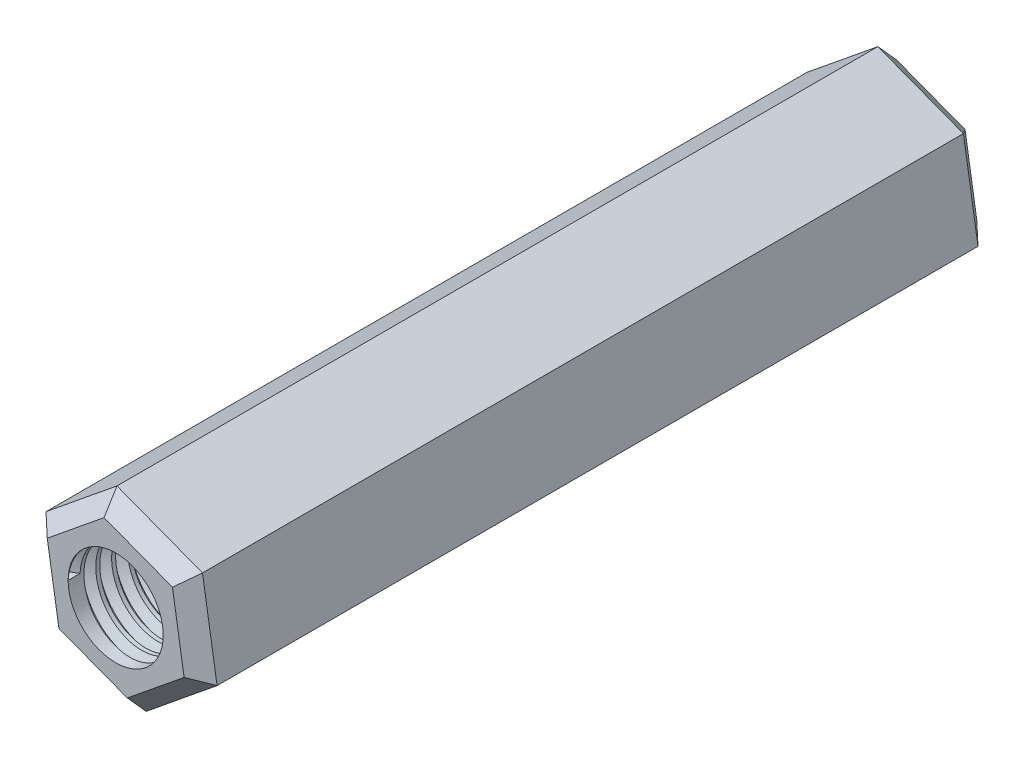
SolidWorks part; units mm, degrees
ref_plane "Plan de face" through (0, 0, 0) normal (0, 0, 1) x (1, 0, 0)
ref_plane "Plan de dessus" through (0, 0, 0) normal (0, 1, 0) x (1, 0, 0)
ref_plane "Plan de droite" through (0, 0, 0) normal (1, 0, 0) x (0, 0, -1)
sketch "Esquisse1" plane through (0, 0, 0) normal (0, 0, 1) x (1, 0, 0)
  line L1 (2.6978, -1.0272) -> (2.2385, 1.8228)
  line L2 (2.2385, 1.8228) -> (-0.4594, 2.85)
  line L3 (-0.4594, 2.85) -> (-2.6978, 1.0272)
  line L4 (-2.6978, 1.0272) -> (-2.2385, -1.8228)
  line L5 (-2.2385, -1.8228) -> (0.4594, -2.85)
  line L6 (0.4594, -2.85) -> (2.6978, -1.0272)
  circle A0 centre (0, 0) radius 2.5 construction
  dimension "D1" = 5
extrude "Boss.-Extru.1" add sketch "Esquisse1" along normal blind 25
sketch3d "Esquisse3D1"
  point P0 (-0.3524, 0.5785, 25)
ref_plane "Plan1" through (0, 0, 25) normal (0, 0, 1) x (1, 0, 0)
sketch "Esquisse2" plane through (0, 0, 25) normal (0, 0, 1) x (1, 0, 0)
  circle A0 centre (0, 0) radius 1.5
  dimension "D1" = 3
extrude "Enlèv. mat.-Extru.1" cut sketch "Esquisse2" against normal up to next
thread "Filetage6" pitch 0.5 method cut profile "Profil de filetage7" start angle 0, offset 0, length 24.5, pitch 0.5, diameter 3
ref_plane "Plan8" through (-1.5, 0, 25) normal (0, -1, 0) x (-1, 0, 0)
sketch "Profil de filetage7" plane through (-1.5, 0, 25) normal (0, -1, 0) x (-1, 0, 0)
  line L0 (0, 0) -> (0, 0.5) construction
  line L1 (0, 0) -> (0.2706, 0.1562)
  line L2 (0.2706, 0.1562) -> (0.2706, 0.2187)
  line L3 (0.2706, 0.2187) -> (0, 0.375)
  line L4 (0.2706, 0.1875) -> (0, 0.1875) construction
  line L11 (0, 0) -> (0, 0.375)
  point P2 (0, 0)
  dimension "Pitch" = 0.5
  dimension "Profile_Angle" = 60
  dimension "Profile_Land" = 0.0625
  dimension "Profile_Height" = 0.2706
chamfer "Chanfrein1" distance 0.5 angle 45 6 edges at (-0.8895, -2.3364, 25) (1.5786, -1.9386, 25) (2.4681, 0.3978, 25) (0.8895, 2.3364, 25) (-1.5786, 1.9386, 25) (-2.4681, -0.3978, 25)
chamfer "Chanfrein2" distance 0.5 angle 45 6 edges at (-1.5786, 1.9386, 0) (-2.4681, -0.3978, 0) (-0.8895, -2.3364, 0) (1.5786, -1.9386, 0) (2.4681, 0.3978, 0) (0.8895, 2.3364, 0)
